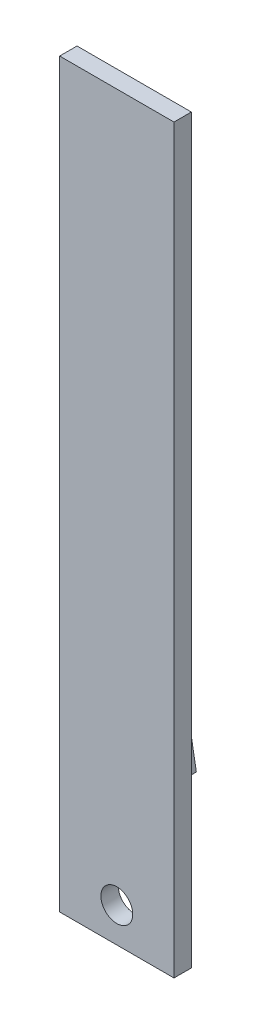
SolidWorks part; units mm, degrees
ref_plane "Front Plane" through (0, 0, 0) normal (0, 0, 1) x (1, 0, 0)
ref_plane "Top Plane" through (0, 0, 0) normal (0, 1, 0) x (1, 0, 0)
ref_plane "Right Plane" through (0, 0, 0) normal (1, 0, 0) x (0, 0, -1)
sketch "Sketch1" plane through (0, 0, 0) normal (0, 0, 1) x (1, 0, 0)
  line L1 (0, 0) -> (-20.8947, 0)
  line L2 (0, 0) -> (0, 135.4765)
  line L3 (0, 135.4765) -> (-20.8947, 135.4765)
  line L4 (-20.8947, 0) -> (-20.8947, 135.4765)
extrude "Boss-Extrude1" add sketch "Sketch1" along normal blind 3.175
sketch "Sketch2" plane through (0, 0, 0) normal (0, 0, -1) x (-1, 0, 0)
  line L0 (20.8947, 0) -> (0, 0) construction
  circle A0 centre (10.4474, 6.3053) radius 2.912
  circle A1 centre (15.1989, 22.4458) radius 3.45
  point P2 (14.4422, 49.406)
  point P5 (10.4474, 0)
  point P8 (16.1908, 35.5915)
  point P9 (15.1989, 29.8495)
  point P10 (15.1989, 22.4458)
  point P11 (10.4474, 6.3053)
extrude "Cut-Extrude2" cut sketch "Sketch2" against normal through all both and the other way through all contours A0
extrude "Boss-Extrude2" add sketch "Sketch2<4>" along normal blind 9.652 contours A1
sketch "Sketch2<4>" plane through (0, 0, 0) normal (0, 0, -1) x (-1, 0, 0) same geometry as "Sketch2"
sketch "Sketch3" plane through (0, 0, -9.652) normal (0, 0, -1) x (-1, 0, 0)
  line L1 (10.9649, 25.9916) -> (10.0111, 20.552)
  line L2 (10.0111, 20.552) -> (14.2451, 17.0061)
  line L3 (14.2451, 17.0061) -> (19.4329, 18.8999)
  line L4 (19.4329, 18.8999) -> (20.3867, 24.3396)
  line L5 (20.3867, 24.3396) -> (16.1527, 27.8855)
  line L6 (16.1527, 27.8855) -> (10.9649, 25.9916)
  circle A0 centre (15.1989, 22.4458) radius 4.7828 construction
extrude "Boss-Extrude3" add sketch "Sketch3" along normal blind 1.27
